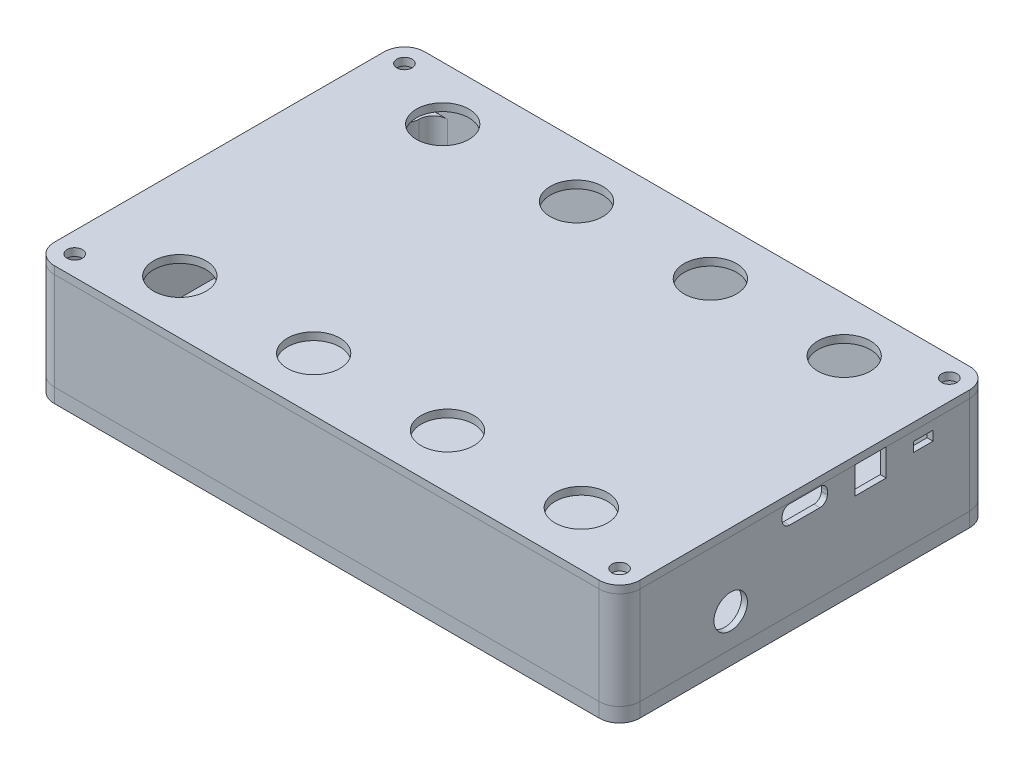
SolidWorks part; units mm, degrees
ref_plane "Front Plane" through (0, 0, 0) normal (0, 0, 1) x (1, 0, 0)
ref_plane "Top Plane" through (0, 0, 0) normal (0, 1, 0) x (1, 0, 0)
ref_plane "Right Plane" through (0, 0, 0) normal (1, 0, 0) x (0, 0, -1)
sketch "pcb" plane through (0, 0, 0) normal (0, 1, 0) x (1, 0, 0)
  line L0 (-14, -27.5) -> (-42, -27.5) construction
  line L1 (-57, -37.5) -> (57, -37.5)
  line L2 (-60, -34.5) -> (-60, 34.5)
  line L3 (-57, 37.5) -> (57, 37.5)
  line L4 (60, -34.5) -> (60, 34.5)
  line L5 (-60, -37.5) -> (60, 37.5) construction
  line L6 (-60, 37.5) -> (60, -37.5) construction
  line L7 (-14, -27.5) -> (14, -27.5) construction
  line L8 (14, -27.5) -> (42, -27.5) construction
  line L9 (-42, -27.5) -> (-60, -27.5) construction
  line L10 (42, -27.5) -> (60, -27.5) construction
  line L11 (-60, 0) -> (60, 0) construction
  arc A0 (-57, -37.5) -> (-60, -34.5) centre (-57, -34.5) cw
  arc A1 (57, -37.5) -> (60, -34.5) centre (57, -34.5) ccw
  arc A2 (57, 37.5) -> (60, 34.5) centre (57, 34.5) cw
  arc A3 (-60, 34.5) -> (-57, 37.5) centre (-57, 34.5) cw
  circle A4 centre (-57, 34.5) radius 1.6
  circle A5 centre (57, 34.5) radius 1.6
  circle A6 centre (57, -34.5) radius 1.6
  circle A7 centre (-57, -34.5) radius 1.6
  circle A8 centre (-42, -27.5) radius 5.5
  circle A9 centre (-14, -27.5) radius 5.5
  circle A10 centre (14, -27.5) radius 5.5
  circle A11 centre (42, -27.5) radius 5.5
  circle A12 centre (-42, 27.5) radius 5.5
  circle A13 centre (-14, 27.5) radius 5.5
  circle A14 centre (14, 27.5) radius 5.5
  circle A15 centre (42, 27.5) radius 5.5
  point P0 (0, 0)
  point P34 (60, 25.1663)
  dimension "D3" = 3
  dimension "D4" = 3
  dimension "D5" = 3
  dimension "D6" = 3
  dimension "D7" = 3.2
  dimension "D9" = 11
  dimension "D10" = 18
  dimension "D1" = 120
  dimension "D2" = 75
  dimension "D8" = 10
sketch "Sketch3" plane through (0, 0, 0) normal (0, 0, 1) x (1, 0, 0)
  line L0 (0, 0) -> (0, 1.6) construction
  line L1 (-57, 0) -> (57, 0) construction
  line L2 (0, 1.6) -> (0, 7) construction
  line L3 (0, 7) -> (0, 8.6) construction
  line L4 (0, 0) -> (0, -13.4) construction
  line L5 (0, -13.4) -> (0, -16.4) construction
  point P4 (0, 0)
  point P10 (0, 0)
  dimension "D1" = 1.6
  dimension "D2" = 3
  dimension "D3" = 13.4
  dimension "D4" = 5.4
  dimension "D5" = 1.6
  dimension "D6" = 25
sketch "Sketch2" plane through (0, 0, 0) normal (0, 1, 0) x (1, 0, 0)
  line L0 (-60, -34.5) -> (-60, 34.5) construction
  line L1 (-57, -37.5) -> (57, -37.5) construction
  line L2 (60, -34.5) -> (60, 34.5) construction
  line L3 (-57, 37.5) -> (57, 37.5) construction
  line L4 (-60, -34.5) -> (-60, 34.5)
  line L5 (-57, -37.5) -> (57, -37.5)
  line L6 (60, -34.5) -> (60, 34.5)
  line L7 (-57, 37.5) -> (57, 37.5)
  line L8 (-61.25, -34.5) -> (-61.25, 34.5)
  line L9 (-57, -38.75) -> (57, -38.75)
  line L10 (61.25, -34.5) -> (61.25, 34.5)
  line L11 (-57, 38.75) -> (57, 38.75)
  arc A0 (-57, 37.5) -> (-60, 34.5) centre (-57, 34.5) ccw construction
  arc A1 (-60, -34.5) -> (-57, -37.5) centre (-57, -34.5) ccw construction
  arc A2 (57, -37.5) -> (60, -34.5) centre (57, -34.5) ccw construction
  arc A3 (60, 34.5) -> (57, 37.5) centre (57, 34.5) ccw construction
  arc A4 (-57, 37.5) -> (-60, 34.5) centre (-57, 34.5) ccw
  arc A5 (-60, -34.5) -> (-57, -37.5) centre (-57, -34.5) ccw
  arc A6 (57, -37.5) -> (60, -34.5) centre (57, -34.5) ccw
  arc A7 (60, 34.5) -> (57, 37.5) centre (57, 34.5) ccw
  arc A8 (-57, 38.75) -> (-61.25, 34.5) centre (-57, 34.5) ccw
  arc A9 (-61.25, -34.5) -> (-57, -38.75) centre (-57, -34.5) ccw
  arc A10 (57, -38.75) -> (61.25, -34.5) centre (57, -34.5) ccw
  arc A11 (61.25, 34.5) -> (57, 38.75) centre (57, 34.5) ccw
  dimension "D1" = 1.25
extrude "Walls" add sketch "Sketch2" against normal up to vertex (13.4 mm away) and the other way up to vertex (7 mm away) up to point (0, -13.4, 0) other way up to point (0, 7, 0)
sketch "Sketch11" plane through (0, 0, 0) normal (0, 1, 0) x (1, 0, 0)
  line L0 (-60, -34.5) -> (-60, -31.5)
  line L1 (-60, -34.5) -> (-60, 34.5) construction
  line L2 (-60, -31.5) -> (-54, -31.5)
  line L3 (-54, -31.5) -> (-54, -37.5)
  line L4 (-57, -37.5) -> (57, -37.5) construction
  line L5 (-54, -37.5) -> (-57, -37.5)
  line L6 (-57, 37.5) -> (-54, 37.5)
  line L7 (-57, 37.5) -> (57, 37.5) construction
  line L8 (-54, 37.5) -> (-54, 31.5)
  line L9 (-54, 31.5) -> (-60, 31.5)
  line L10 (-60, 31.5) -> (-60, 34.5)
  line L11 (60, -31.5) -> (54, -31.5)
  line L12 (60, -34.5) -> (60, 34.5) construction
  line L13 (54, -31.5) -> (54, -37.5)
  line L14 (54, -37.5) -> (57, -37.5)
  line L15 (60, -31.5) -> (60, -34.5)
  line L16 (57, 37.5) -> (54, 37.5)
  line L17 (54, 37.5) -> (54, 31.5)
  line L18 (54, 31.5) -> (60, 31.5)
  line L19 (60, 31.5) -> (60, 34.5)
  arc A0 (-60, -34.5) -> (-57, -37.5) centre (-57, -34.5) ccw construction
  arc A1 (-60, -34.5) -> (-57, -37.5) centre (-57, -34.5) ccw
  arc A2 (-57, 37.5) -> (-60, 34.5) centre (-57, 34.5) ccw construction
  arc A3 (-57, 37.5) -> (-60, 34.5) centre (-57, 34.5) ccw
  circle A4 centre (-57, 34.5) radius 1.6 construction
  circle A5 centre (-57, 34.5) radius 1.6
  circle A6 centre (-57, -34.5) radius 1.6 construction
  circle A7 centre (-57, -34.5) radius 1.6
  arc A8 (57, -37.5) -> (60, -34.5) centre (57, -34.5) ccw construction
  arc A9 (57, -37.5) -> (60, -34.5) centre (57, -34.5) ccw
  circle A10 centre (57, -34.5) radius 1.6 construction
  circle A11 centre (57, -34.5) radius 1.6
  arc A12 (60, 34.5) -> (57, 37.5) centre (57, 34.5) ccw construction
  arc A13 (60, 34.5) -> (57, 37.5) centre (57, 34.5) ccw
  circle A14 centre (57, 34.5) radius 1.6 construction
  circle A15 centre (57, 34.5) radius 1.6
  dimension "D1" = 6
  dimension "D2" = 6
  dimension "D3" = 6
  dimension "D4" = 6
extrude "Boss-Extrude4" add sketch "Sketch11" against normal up to surface (13.4 mm away) up to face at (0, -13.4, 0)
fillet "Fillet1" radius 3 12 edges at (60, -6.7, -31.5) (54, -6.7, -37.5) (-54, -6.7, -37.5) (-60, -6.7, -31.5) (-54, -6.7, 37.5) (-60, -6.7, 31.5) (54, -6.7, 37.5) (60, -6.7, 31.5) (54, -6.7, 31.5) (-54, -6.7, 31.5) (-54, -6.7, -31.5) (54, -6.7, -31.5)
sketch "Sketch8" plane through (61.25, 0, 0) normal (1, 0, 0) x (0, 0, -1)
  line L0 (0, 1.6) -> (0, 7) construction
  line L1 (-3.17, 3.17) -> (3.17, 3.17)
  line L2 (-4.47, 4.47) -> (-4.47, 5.23)
  line L3 (-3.17, 6.53) -> (3.17, 6.53)
  line L4 (4.47, 4.47) -> (4.47, 5.23)
  line L5 (-4.47, 3.17) -> (4.47, 6.53) construction
  line L6 (-4.47, 6.53) -> (4.47, 3.17) construction
  line L8 (0, 0) -> (0, 1.6) construction
  line L9 (0, 0) -> (0, 1.6) construction
  line L11 (16.8, 1.6) -> (10.8, 1.6)
  line L12 (16.8, 1.6) -> (16.8, 6.82)
  line L13 (16.8, 6.82) -> (10.8, 6.82)
  line L14 (10.8, 1.6) -> (10.8, 6.82)
  line L15 (-37.5, 0) -> (37.5, 0) construction
  line L16 (0, 0) -> (0, -13.4) construction
  line L18 (23, 4.87) -> (26.6, 4.87)
  line L19 (23, 4.87) -> (23, 3.37)
  line L20 (23, 3.37) -> (26.6, 3.37)
  line L21 (26.6, 4.87) -> (26.6, 3.37)
  arc A0 (3.17, 6.53) -> (4.47, 5.23) centre (3.17, 5.23) cw
  arc A1 (3.17, 3.17) -> (4.47, 4.47) centre (3.17, 4.47) ccw
  arc A2 (-3.17, 3.17) -> (-4.47, 4.47) centre (-3.17, 4.47) cw
  arc A3 (-4.47, 5.23) -> (-3.17, 6.53) centre (-3.17, 5.23) cw
  circle A4 centre (-15.5, -6.55) radius 3.25
  point P0 (0, 4.85)
  point P10 (13.8, 1.6)
  dimension "D4" = 1.3
  dimension "D5" = 1.3
  dimension "D6" = 1.3
  dimension "D7" = 1.3
  dimension "D11" = 6.5
  dimension "D1" = 3.36
  dimension "D2" = 8.94
  dimension "D3" = 3.25
  dimension "D8" = 13.8
  dimension "D9" = 6
  dimension "D10" = 5.22
  dimension "D12" = 6.55
  dimension "D13" = 15.5
  dimension "D14" = 1.5
  dimension "D15" = 3.6
  dimension "D16" = 1.77
  dimension "D17" = 9.2
extrude "Cut-Extrude3" cut sketch "Sketch8" along direction (1, 0, 0) on the side against the normal up to surface (1.25 mm away) up to face at (60, -1.6, 0)
sketch "Sketch10" plane through (-61.25, 0, 0) normal (-1, 0, 0) x (0, 0, 1)
  line L0 (-34.5, 7) -> (34.5, 7) construction
  line L1 (5.84, 1.6) -> (26.16, 1.6)
  line L2 (5.84, 1.6) -> (5.84, 7)
  line L3 (5.84, 7) -> (26.16, 7)
  line L4 (26.16, 1.6) -> (26.16, 7)
  line L6 (-5.84, 1.6) -> (-26.16, 1.6)
  line L7 (-5.84, 1.6) -> (-5.84, 7)
  line L8 (-5.84, 7) -> (-26.16, 7)
  line L9 (-26.16, 1.6) -> (-26.16, 7)
  line L10 (0, 0) -> (0, 1.6) construction
  line L15 (0, 0) -> (0, 1.6) construction
  line L16 (-5.84, 1.6) -> (0, 1.6) construction
  line L17 (0, 1.6) -> (5.84, 1.6) construction
  line L22 (-1.8, 4.87) -> (1.8, 4.87)
  line L23 (-1.8, 4.87) -> (-1.8, 3.37)
  line L24 (-1.8, 3.37) -> (1.8, 3.37)
  line L25 (1.8, 4.87) -> (1.8, 3.37)
  point P10 (0, 3.37)
  dimension "D1" = 20.32
  dimension "D2" = 20.32
  dimension "D3" = 11.68
  dimension "D4" = 3.6
  dimension "D5" = 1.5
  dimension "D6" = 1.77
extrude "Cut-Extrude4" cut sketch "Sketch10" against normal up to next
other "Move Face3" flip direction yes face at (60.625, 4.12, -23) face at (60.625, 4.87, -24.8) face at (60.625, 4.12, -26.6) face at (60.625, 3.37, -24.8) offset 0.25 parameters "D1"=0.25
other "Move Face4" flip direction yes face at (60, -6.55, 12.25) face at (60.625, 3.6854, 3.9546) face at (60.625, 4.85, 4.47) face at (60.625, 6.0146, 3.9546) face at (60.625, 6.53, 0) face at (60.625, 3.6854, -3.9546) face at (60.625, 3.17, 0) face at (60.625, 4.85, -4.47) face at (60.625, 6.0146, -3.9546) face at (60.625, 1.6, -13.8) face at (60.625, 4.21, -16.8) face at (60.625, 4.21, -10.8) face at (60.625, 6.82, -13.8) offset 0.25 parameters "D1"=0.25
other "Move Face1" flip direction yes face at (-60.625, 4.3, 26.16) face at (-60.625, 1.6, 16) face at (-60.625, 4.3, 5.84) face at (-60.625, 4.3, -26.16) face at (-60.625, 1.6, -16) face at (-60.625, 4.3, -5.84) offset 1 parameters "D1"=1
other "Move Face2" flip direction yes face at (-60.625, 4.12, -1.8) face at (-60.625, 4.87, 0) face at (-60.625, 3.37, 0) face at (-60.625, 4.12, 1.8) offset 0.25 parameters "D1"=0.25
sketch "Sketch4" plane through (0, -13.4, 0) normal (0, -1, 0) x (1, 0, 0)
  line L4 (-57, -38.75) -> (57, -38.75)
  line L5 (61.25, -34.5) -> (61.25, 34.5)
  line L6 (57, 38.75) -> (-57, 38.75)
  line L7 (-61.25, 34.5) -> (-61.25, -34.5)
  line L8 (-57, -38.75) -> (57, -38.75)
  line L9 (61.25, -34.5) -> (61.25, 34.5)
  line L10 (57, 38.75) -> (-57, 38.75)
  line L11 (-61.25, 34.5) -> (-61.25, -34.5)
  circle A0 centre (57, -34.5) radius 2.15
  circle A1 centre (-57, -34.5) radius 2.15
  circle A2 centre (-57, 34.5) radius 2.15
  circle A3 centre (57, 34.5) radius 2.15
  arc A4 (-61.25, -34.5) -> (-57, -38.75) centre (-57, -34.5) ccw
  arc A5 (57, -38.75) -> (61.25, -34.5) centre (57, -34.5) ccw
  arc A6 (61.25, 34.5) -> (57, 38.75) centre (57, 34.5) ccw
  arc A7 (-57, 38.75) -> (-61.25, 34.5) centre (-57, 34.5) ccw
  arc A8 (-61.25, -34.5) -> (-57, -38.75) centre (-57, -34.5) ccw
  arc A9 (57, -38.75) -> (61.25, -34.5) centre (57, -34.5) ccw
  arc A10 (61.25, 34.5) -> (57, 38.75) centre (57, 34.5) ccw
  arc A11 (-57, 38.75) -> (-61.25, 34.5) centre (-57, 34.5) ccw
  dimension "D2" = 4.3
  dimension "D1" = 0
extrude "Bottom Lid" add sketch "Sketch4" along normal blind 3 separate body
sketch "Sketch5" plane through (0, 7, 0) normal (0, 1, 0) x (1, 0, 0)
  line L4 (57, 38.75) -> (-57, 38.75)
  line L5 (61.25, -34.5) -> (61.25, 34.5)
  line L6 (-57, -38.75) -> (57, -38.75)
  line L7 (-61.25, 34.5) -> (-61.25, -34.5)
  line L12 (57, 38.75) -> (-57, 38.75)
  line L13 (61.25, -34.5) -> (61.25, 34.5)
  line L14 (-57, -38.75) -> (57, -38.75)
  line L15 (-61.25, 34.5) -> (-61.25, -34.5)
  circle A3 centre (42, 27.5) radius 5.5 construction
  circle A15 centre (42, 27.5) radius 5.5
  circle A16 centre (-14, 27.5) radius 5.5 construction
  circle A17 centre (14, 27.5) radius 5.5 construction
  circle A18 centre (-14, 27.5) radius 5.5
  circle A19 centre (14, 27.5) radius 5.5
  circle A20 centre (-42, 27.5) radius 5.5 construction
  circle A21 centre (-42, 27.5) radius 5.5
  circle A22 centre (42, -27.5) radius 5.5 construction
  circle A23 centre (14, -27.5) radius 5.5 construction
  circle A24 centre (-14, -27.5) radius 5.5 construction
  circle A25 centre (-42, -27.5) radius 5.5 construction
  circle A26 centre (42, -27.5) radius 5.5
  circle A27 centre (14, -27.5) radius 5.5
  circle A28 centre (-14, -27.5) radius 5.5
  circle A29 centre (-42, -27.5) radius 5.5
  circle A30 centre (-57, -34.5) radius 1.6 construction
  circle A31 centre (-57, 34.5) radius 1.6 construction
  circle A32 centre (57, 34.5) radius 1.6 construction
  circle A33 centre (57, -34.5) radius 1.6 construction
  circle A34 centre (-57, -34.5) radius 1.6
  circle A35 centre (-57, 34.5) radius 1.6
  circle A36 centre (57, 34.5) radius 1.6
  circle A37 centre (57, -34.5) radius 1.6
  arc A38 (-57, 38.75) -> (-61.25, 34.5) centre (-57, 34.5) ccw
  arc A39 (61.25, 34.5) -> (57, 38.75) centre (57, 34.5) ccw
  arc A40 (57, -38.75) -> (61.25, -34.5) centre (57, -34.5) ccw
  arc A41 (-61.25, -34.5) -> (-57, -38.75) centre (-57, -34.5) ccw
  arc A42 (-57, 38.75) -> (-61.25, 34.5) centre (-57, 34.5) ccw
  arc A43 (61.25, 34.5) -> (57, 38.75) centre (57, 34.5) ccw
  arc A44 (57, -38.75) -> (61.25, -34.5) centre (57, -34.5) ccw
  arc A45 (-61.25, -34.5) -> (-57, -38.75) centre (-57, -34.5) ccw
  dimension "D1" = 0
extrude "Top Lid" add sketch "Sketch5" along normal blind 1.6 separate body
equation "\"D2@Sketch10\"=\"D1@Sketch10\""
equation "\"D2@Sketch11\"=\"D1@Sketch11\""
equation "\"D3@Sketch11\"=\"D1@Sketch11\""
equation "\"D4@Sketch11\"=\"D1@Sketch11\""
